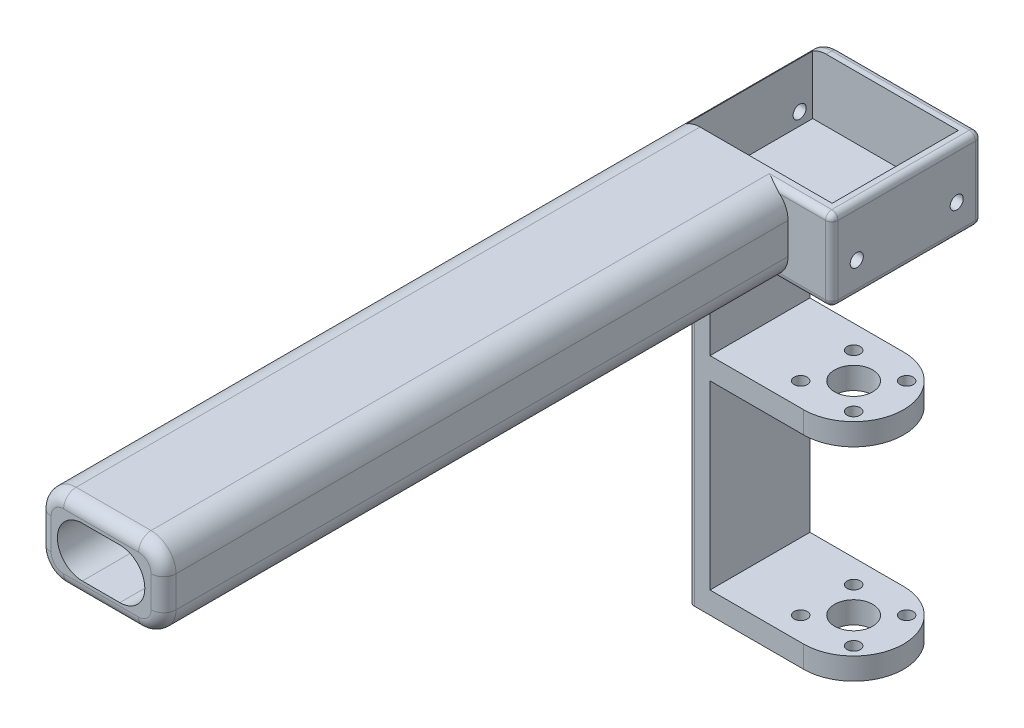
SolidWorks part; units mm, degrees
ref_plane "前视基准面" through (0, 0, 0) normal (0, 0, 1) x (1, 0, 0)
ref_plane "上视基准面" through (0, 0, 0) normal (0, 1, 0) x (1, 0, 0)
ref_plane "右视基准面" through (0, 0, 0) normal (1, 0, 0) x (0, 0, -1)
sketch "草图1" plane through (0, 0, 0) normal (0, 1, 0) x (1, 0, 0)
  line L0 (0, 8) -> (-15, 8)
  line L1 (0, 0) -> (-20.7875, 0) construction
  line L2 (0, -8) -> (-15, -8)
  line L3 (-15, 8) -> (-15, -8)
  line L4 (0, 8) -> (0, -13.8508) construction
  line L5 (0, 0) -> (-10.1753, 10.1753) construction
  line L6 (0, 0) -> (-6.4674, -6.4674) construction
  line L7 (4.2426, 4.2426) -> (-5.3918, -5.3918) construction
  arc A0 (0, -8) -> (0, 8) centre (0, 0) ccw
  circle A1 centre (0, 0) radius 6 construction
  circle A6 centre (0, 0) radius 3.05
  circle A7 centre (-4.2426, 4.2426) radius 1.05
  circle A9 centre (-4.2426, -4.2426) radius 1.05
  circle A10 centre (4.2426, -4.2426) radius 1.05
  circle A11 centre (4.2426, 4.2426) radius 1.05
  dimension "D1" = 16
  dimension "D3" = 12
  dimension "D8" = 6.1
  dimension "D10" = 2.1
  dimension "D13" = 2.1
  dimension "D2" = 15
  dimension "D9" = 45
  dimension "D12" = 45
extrude "凸台-拉伸1" add sketch "草图1" along normal blind 3.5
ref_plane "基准面4" through (0, 18, 0) normal (0, 1, 0) x (1, 0, 0)
mirror "镜向4" about plane through (0, 18, 0) normal (0, 1, 0) of bodies 101
sketch "草图2" plane through (-15, 0, 0) normal (-1, 0, 0) x (0, 0, 1)
  line L0 (-8, 0) -> (8, 0) construction
  line L2 (-8, 36) -> (-8, 0)
  line L3 (-8, 0) -> (8, 0)
  line L4 (8, 36) -> (8, 0)
  line L5 (8, 3.5) -> (8, 0) construction
  line L8 (-8, 36) -> (-8, 56)
  line L9 (-8, 56) -> (8, 56)
  line L10 (8, 36) -> (8, 56)
  dimension "D1" = 20
extrude "凸台-拉伸2" add sketch "草图2" along normal blind 3.5
sketch "草图3" plane through (0, 3.5, 0) normal (0, 1, 0) x (1, 0, 0)
  line L0 (0, -8) -> (10.05, -8)
  line L1 (0, 8) -> (10.05, 8)
  line L2 (10.05, -8) -> (10.05, 8)
  line L3 (0, 8) -> (-15, 8)
  line L4 (-15, 8) -> (-15, -8)
  line L5 (-15, -8) -> (0, -8)
  arc A1 (0, -8) -> (0, 8) centre (0, 0) ccw
  arc A2 (0, -8) -> (0, 8) centre (0, 0) ccw
  dimension "D2" = 25.05
  dimension "D3" = 25.05
  dimension "D1" = 0
sketch "草图4" plane through (0, 32.5, 0) normal (0, -1, 0) x (1, 0, 0)
  line L0 (0, -8) -> (10.05, -8) construction
  line L1 (10.05, 8) -> (10.05, -8) construction
  line L2 (0, 8) -> (10.05, 8) construction
  line L3 (0, 8) -> (10.05, 8)
  line L4 (10.05, 8) -> (10.05, -8)
  line L5 (0, -8) -> (10.05, -8)
  arc A0 (0, -8) -> (0, 8) centre (0, 0) ccw construction
  arc A1 (0, -8) -> (0, 8) centre (0, 0) ccw
sketch "草图5" plane through (0, 0, 8) normal (0, 0, 1) x (1, 0, 0)
  line L1 (10.05, 32.5) -> (-18.5, 32.5)
  line L2 (-18.5, 0) -> (-18.5, 56) construction
  line L4 (-18.5, 96.5) -> (10.05, 96.5)
  line L5 (10.05, 96.5) -> (10.05, 32.5)
  line L6 (-18.95, 96.5) -> (-18.95, 32.5)
  line L7 (-18.95, 96.5) -> (-18.5, 96.5)
  line L8 (-18.95, 32.5) -> (-18.5, 32.5)
  dimension "D1" = 64
sketch "草图12" plane through (0, 3.5, 0) normal (0, 1, 0) x (1, 0, 0)
  line L0 (0, 3.05) -> (11.7827, 3.05)
  line L1 (0, -3.05) -> (11.7827, -3.05)
  line L2 (11.7827, 3.05) -> (11.7827, -3.05)
  circle A0 centre (0, 0) radius 3.05 construction
  arc A1 (0, -3.05) -> (0, 3.05) centre (0, 0) ccw
sketch "草图14" plane through (-15, 0, 0) normal (1, 0, 0) x (0, 0, -1)
  line L0 (8, 56) -> (8, 36) construction
  line L5 (-8, 56) -> (8, 56)
  line L6 (-8, 56) -> (-8, 45.9006)
  line L7 (-8, 45.9006) -> (8, 45.9006)
  line L8 (8, 56) -> (8, 45.9006)
  dimension "D1" = 10.0994
sketch "草图16" plane through (0, 56, 0) normal (0, 1, 0) x (1, 0, 0)
  line L0 (-18.5, 0) -> (19.5627, 0) construction
  line L1 (-18.5, -8) -> (-18.5, 8) construction
  line L2 (-18.5, -12) -> (-18.5, 12)
  line L3 (-18.5, 12) -> (8.5, 12)
  line L4 (-18.5, -12) -> (8.5, -12)
  line L5 (8.5, 12) -> (8.5, -12)
  dimension "D1" = 27
  dimension "D2" = 12
extrude "凸台-拉伸5" add sketch "草图16" along normal blind 3
sketch "草图17" plane through (0, 59, 0) normal (0, 1, 0) x (1, 0, 0)
  line L0 (8.5, 12) -> (-18.5, 12) construction
  line L1 (-16.5, 10) -> (6.5, 10)
  line L2 (-16.5, 10) -> (-16.5, -10)
  line L3 (-16.5, -10) -> (6.5, -10)
  line L4 (6.5, 10) -> (6.5, -10)
  line L5 (-18.5, -12) -> (8.5, -12) construction
  line L6 (-18.5, 12) -> (-18.5, -12) construction
  line L7 (8.5, -12) -> (8.5, 12) construction
  line L12 (8.5, -12) -> (8.5, 12)
  line L13 (8.5, 12) -> (-18.5, 12)
  line L14 (-18.5, 12) -> (-18.5, -12)
  line L15 (-18.5, -12) -> (8.5, -12)
  line L16 (8.5, -12) -> (8.5, 12)
  line L17 (8.5, 12) -> (-18.5, 12)
  line L18 (-18.5, 12) -> (-18.5, -12)
  line L19 (-18.5, -12) -> (8.5, -12)
  dimension "D1" = 2
  dimension "D2" = 2
  dimension "D3" = 2
  dimension "D4" = 2
  dimension "D5" = 0
extrude "凸台-拉伸6" add sketch "草图17" along normal blind 10
sketch "草图18" plane through (-16.5, 0, 0) normal (1, 0, 0) x (0, 0, -1)
  line L0 (0, 69) -> (0, 66.7088) construction
  line L4 (-10, 59) -> (10, 59)
  line L5 (10, 59) -> (10, 69)
  line L6 (10, 69) -> (-10, 69)
  line L7 (-10, 69) -> (-10, 59)
  line L8 (-10, 59) -> (10, 59) construction
  line L9 (10, 59) -> (10, 69) construction
  line L10 (10, 69) -> (-10, 69) construction
  line L11 (-10, 69) -> (-10, 59) construction
  circle A0 centre (-8, 61) radius 1.05
  circle A1 centre (8, 61) radius 1.05
  dimension "D2" = 2.1
  dimension "D3" = 2
  dimension "D4" = 16
  dimension "D1" = 0
extrude "切除-拉伸1" cut sketch "草图18" against normal mid plane 60
sketch "草图19" plane through (0, 0, 12) normal (0, 0, 1) x (1, 0, 0)
  line L0 (-18.5, 56) -> (8.5, 56) construction
  line L1 (-18.5, 69) -> (1.5, 69)
  line L2 (-18.5, 69) -> (-18.5, 56)
  line L3 (-18.5, 56) -> (1.5, 56)
  line L4 (1.5, 69) -> (1.5, 56)
  dimension "D1" = 13
  dimension "D2" = 20
extrude "凸台-拉伸7" add sketch "草图19" along normal blind 100
fillet "圆角1" radius 4 2 edges at (-18.5, 56, 60) (1.5, 69, 62)
fillet "圆角2" radius 4 2 edges at (-18.5, 69, 50) (1.5, 56, 62)
fillet "圆角3" radius 1 5 edges at (-18.5, 60.5, -12) (-17.3284, 67.8284, -12) (3, 69, 12) (8.5, 69, 0) (-3, 69, -12)
fillet "圆角4" radius 1 2 edges at (-18.5, 29.975, 8) (-18.5, 28, -8)
sketch "草图20" plane through (0, 0, 112) normal (0, 0, 1) x (1, 0, 0)
  line L0 (-18.5, 62.5) -> (-15.5, 62.5) construction
  line L1 (-18.5, 65) -> (-18.5, 60) construction
  line L2 (-8.5, 69) -> (-8.5, 66.5) construction
  line L3 (-2.5, 69) -> (-14.5, 69) construction
  line L4 (-11.5, 66.5) -> (-5.5, 66.5)
  line L5 (-11.5, 58.5) -> (-5.5, 58.5)
  line L6 (-8.5, 58.5) -> (-8.5, 51.0236) construction
  line L7 (-1.5, 62.5) -> (1.9626, 62.5) construction
  arc A0 (-11.5, 66.5) -> (-11.5, 58.5) centre (-11.5, 62.5) ccw
  arc A1 (-5.5, 58.5) -> (-5.5, 66.5) centre (-5.5, 62.5) ccw
  dimension "D1" = 8
  dimension "D3" = 8
  dimension "D2" = 3
  dimension "D4" = 3
extrude "切除-拉伸2" cut sketch "草图20" against normal blind 80
fillet "圆角5" radius 2 8 edges at (0.3284, 57.1716, 112) (-8.5, 56, 112) (-17.3284, 57.1716, 112) (-18.5, 62.5, 112) (-17.3284, 67.8284, 112) (0.3284, 67.8284, 112) (1.5, 62.5, 112) (-8.5, 69, 112)
fillet "圆角6" radius 1 8 edges at (8.2071, 68.7071, -11.7071) (8.2071, 68.7071, 11.7071) (-18.5, 56, -9) (-18.2071, 56, -11.7071) (8.5, 62, 12) (8.5, 62, -12) (8.5, 56, 0) (-4.5, 56, -12)
fillet "圆角7" radius 1 2 edges at (8.2071, 56.2929, 11.7071) (2.5, 56, 12)
ref_plane "基准面5" through (-5, 0, 0) normal (1, 0, 0) x (0, 0, -1)
sketch "草图21" plane through (-5, 0, 0) normal (1, 0, 0) x (0, 0, -1)
  line L0 (-10, 68.4641) -> (-10, 70.1536)
  line L1 (-10, 70.1536) -> (10, 70.1536)
  line L2 (10, 70.1536) -> (10, 68.4641)
  line L4 (10, 59) -> (10, 68.4641)
  line L5 (10, 68.4641) -> (-10, 68.4641)
  line L6 (-10, 68.4641) -> (-10, 59)
  line L7 (-10, 59) -> (10, 59)
  line L8 (10, 59) -> (10, 68.4641)
  line L10 (-10, 68.4641) -> (-10, 59)
  line L11 (-10, 59) -> (10, 59)
  dimension "D1" = 0
extrude "切除-拉伸3" cut sketch "草图21" against normal mid plane 23.2
ref_plane "基准面6" through (0, 0, 0) normal (0, 0, -1) x (-1, 0, 0)
ref_plane "基准面7" through (0, 0, 0) normal (0, 0, -1) x (-1, 0, 0)
sketch "草图23" plane through (0, 0, 0) normal (0, 0, -1) x (-1, 0, 0)
  line L4 (-6.6, 59) -> (16.6, 59)
  line L5 (16.6, 59) -> (16.6, 68.4044)
  line L6 (14.5, 69) -> (-6.6, 69)
  line L7 (-6.6, 69) -> (-6.6, 59)
  line L8 (-6.6, 59) -> (16.6, 59)
  line L9 (16.6, 59) -> (16.6, 68.4044)
  line L10 (14.5, 69) -> (-6.6, 69)
  line L11 (-6.6, 69) -> (-6.6, 59)
  arc A1 (16.6, 68.4044) -> (14.5, 69) centre (14.5, 65) ccw
  arc A2 (16.6, 68.4044) -> (14.5, 69) centre (14.5, 65) ccw
  dimension "D1" = 0
extrude "切除-拉伸4" cut sketch "草图23" against normal mid plane 20.2
ref_plane "基准面8" through (-5, 0, 0) normal (-1, 0, 0) x (0, 0, 1)
sketch "草图24" plane through (-5, 0, 0) normal (-1, 0, 0) x (0, 0, 1)
  line L4 (10.1, 69) -> (-10.1, 69)
  line L5 (-10.1, 69) -> (-10.1, 59)
  line L6 (-10.1, 59) -> (10.1, 59)
  line L7 (10.1, 59) -> (10.1, 69)
  line L8 (10.1, 69) -> (-10.1, 69)
  line L9 (-10.1, 69) -> (-10.1, 59)
  line L10 (-10.1, 59) -> (10.1, 59)
  line L11 (10.1, 59) -> (10.1, 69)
  dimension "D1" = 0
extrude "切除-拉伸6" cut sketch "草图24" against normal mid plane 23.3
